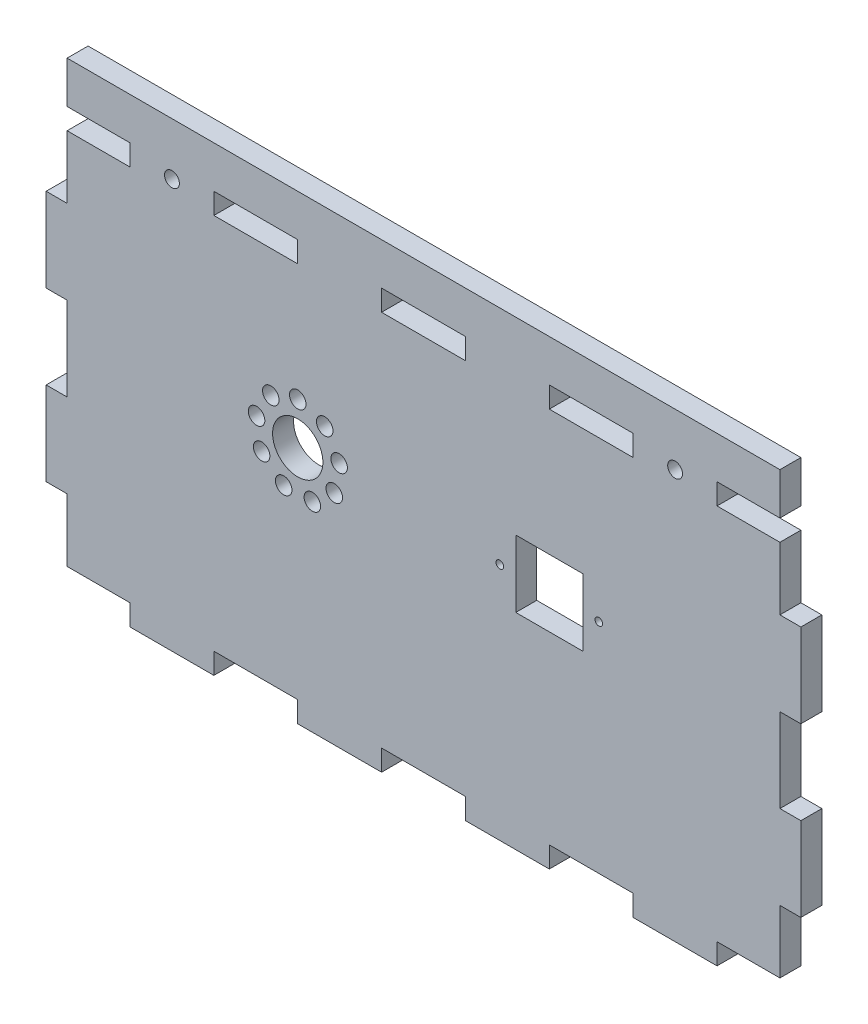
SolidWorks part; units mm, degrees
ref_plane "Front Plane" through (0, 0, 0) normal (0, 0, 1) x (1, 0, 0)
ref_plane "Top Plane" through (0, 0, 0) normal (0, 1, 0) x (1, 0, 0)
ref_plane "Right Plane" through (0, 0, 0) normal (1, 0, 0) x (0, 0, -1)
sketch "Sketch1" plane through (0, 0, 0) normal (0, 0, 1) x (1, 0, 0)
  line L1 (0, 0) -> (228.6, 0)
  line L2 (0, 0) -> (0, 139.7)
  line L3 (0, 139.7) -> (228.6, 139.7)
  line L4 (228.6, 0) -> (228.6, 139.7)
  dimension "D1" = 228.6
  dimension "D2" = 139.7
extrude "Boss-Extrude1" add sketch "Sketch1" along normal blind 6.35
sketch "Sketch5" plane through (0, 0, 6.35) normal (0, 0, 1) x (1, 0, 0)
  line L1 (0, 0) -> (6.35, 0)
  line L2 (0, 0) -> (0, 25.4)
  line L3 (0, 25.4) -> (6.35, 25.4)
  line L4 (6.35, 0) -> (6.35, 25.4)
  dimension "D1" = 25.4
  dimension "D2" = 6.35
extrude "Cut-Extrude4" cut sketch "Sketch5" against normal blind 6.35
sketch "Sketch6" plane through (0, 0, 6.35) normal (0, 0, 1) x (1, 0, 0)
  line L1 (0, 0) -> (25.4, 0)
  line L2 (0, 0) -> (0, 6.35)
  line L3 (0, 6.35) -> (25.4, 6.35)
  line L4 (25.4, 0) -> (25.4, 6.35)
  dimension "D1" = 6.35
  dimension "D2" = 25.4
extrude "Cut-Extrude5" cut sketch "Sketch6" against normal blind 6.35
pattern_linear "LPattern5" count 3 spacing 50.8 along (0, 1, 0) count 2 spacing 222.25 along (1, 0, 0) of "Cut-Extrude4"
pattern_linear "LPattern6" count 5 spacing 50.8 along (1, 0, 0) count 2 spacing 120.65 along (0, 1, 0) of "Cut-Extrude5"
sketch "Sketch7" plane through (0, 0, 6.35) normal (0, 0, 1) x (1, 0, 0)
  line L1 (6.35, 120.65) -> (0, 120.65)
  line L2 (6.35, 120.65) -> (6.35, 139.7)
  line L3 (6.35, 139.7) -> (0, 139.7)
  line L4 (0, 120.65) -> (0, 139.7)
  dimension "D1" = 6.35
  dimension "D2" = 19.05
extrude "Cut-Extrude6" cut sketch "Sketch7" against normal blind 6.35
sketch "Sketch8" plane through (0, 0, 6.35) normal (0, 0, 1) x (1, 0, 0)
  line L1 (228.6, 139.7) -> (222.25, 139.7)
  line L2 (228.6, 139.7) -> (228.6, 120.65)
  line L3 (228.6, 120.65) -> (222.25, 120.65)
  line L4 (222.25, 139.7) -> (222.25, 120.65)
extrude "Cut-Extrude7" cut sketch "Sketch8" against normal blind 6.35
hole_wizard "#8 Clearance Hole1" positions "Sketch10" profile "Sketch9" hole size "#8" standard "ANSI Inch"
sketch "Sketch10" plane through (0, 0, 6.35) normal (0, 0, 1) x (1, 0, 0)
  line L0 (203.2, 127) -> (203.2, 120.65) construction
  line L1 (222.25, 127) -> (203.2, 127) construction
  line L2 (25.4, 120.65) -> (25.4, 127) construction
  line L3 (76.2, 127) -> (50.8, 127) construction
  point P0 (38.1, 123.825)
  point P2 (190.5, 123.825)
  point P7 (203.2, 123.825)
  point P10 (25.4, 123.825)
  dimension "D1" = 12.7
  dimension "D2" = 3.175
  dimension "D3" = 12.7
  dimension "D4" = 3.175
sketch "Sketch9" plane through (38.1, 123.825, 6.35) normal (1, 0, 0) x (0, -1, 0)
  line L0 (0, 0) -> (0, 11.5107)
  line L1 (0, 11.5107) -> (2.2479, 10.16)
  line L2 (2.2479, 10.16) -> (2.2479, 0)
  line L5 (2.2479, 0) -> (0, 0)
  line L10 (0, 11.5107) -> (-2.2479, 10.16) construction
  line L11 (0, -6.35) -> (0, 107.95) construction
  dimension "Hole Dia." = 4.4958
  dimension "Hole Depth" = 10.16
  dimension "Drill Angle" = 118
sketch "Sketch11" plane through (0, 0, 6.35) normal (0, 0, 1) x (1, 0, 0)
  line L0 (101.6, 120.65) -> (127, 120.65) construction
  line L1 (142.24, 82.55) -> (162.56, 82.55)
  line L2 (142.24, 82.55) -> (142.24, 62.23)
  line L3 (142.24, 62.23) -> (162.56, 62.23)
  line L4 (162.56, 82.55) -> (162.56, 62.23)
  line L6 (0, 101.6) -> (0, 76.2) construction
  circle A0 centre (137.414, 72.39) radius 1.143
  circle A1 centre (167.386, 72.39) radius 1.143
  point P6 (152.4, 82.55)
  point P13 (162.56, 72.39)
  point P14 (142.24, 72.39)
  dimension "D5" = 2.286
  dimension "D6" = 2.286
  dimension "D7" = 14.986
  dimension "D8" = 14.986
  dimension "D1" = 38.1
  dimension "D2" = 20.32
  dimension "D3" = 20.32
  dimension "D4" = 152.4
extrude "Cut-Extrude8" cut sketch "Sketch11" against normal blind 7.62
sketch "Sketch12" plane through (0, 0, 6.35) normal (0, 0, 1) x (1, 0, 0)
  line L0 (0, 101.6) -> (0, 76.2) construction
  circle A0 centre (76.2, 72.39) radius 7.62
  dimension "D1" = 15.24
  dimension "D2" = 76.2
extrude "Cut-Extrude9" cut sketch "Sketch12" against normal blind 7.62
sketch "Sketch13" plane through (0, 0, 6.35) normal (0, 0, 1) x (1, 0, 0)
  circle A0 centre (76.2, 85.09) radius 2.5
  circle A1 centre (84.3739, 82.1477) radius 2.5
  circle A2 centre (88.7442, 74.6396) radius 2.5
  circle A3 centre (87.266, 66.079) radius 2.5
  circle A4 centre (80.6309, 60.4713) radius 2.5
  circle A5 centre (71.9436, 60.4405) radius 2.5
  circle A6 centre (65.2689, 66.001) radius 2.5
  circle A7 centre (63.7301, 74.551) radius 2.5
  circle A8 centre (68.0471, 82.0899) radius 2.5
  circle A9 centre (76.2, 72.39) radius 7.62 construction
  point P20 (76.245, 72.39)
  dimension "D1" = 5
  dimension "D3" = 12.7
  dimension "D4" = 0
  dimension "D2" = 9
extrude "Cut-Extrude10" cut sketch "Sketch13" against normal blind 7.62
